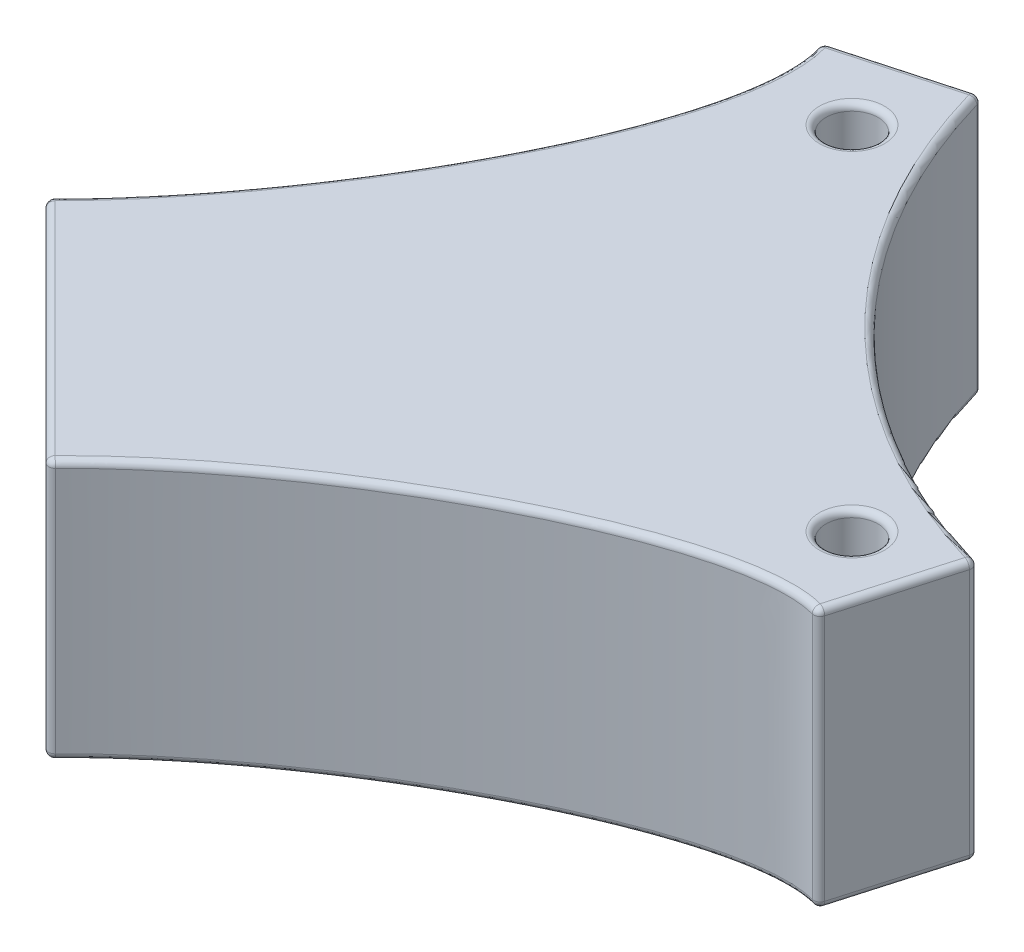
SolidWorks part; units mm, degrees
ref_plane "Front Plane" through (0, 0, 0) normal (0, 0, 1) x (1, 0, 0)
ref_plane "Top Plane" through (0, 0, 0) normal (0, 1, 0) x (1, 0, 0)
ref_plane "Right Plane" through (0, 0, 0) normal (1, 0, 0) x (0, 0, -1)
sketch "Sketch1" plane through (0, 0, 0) normal (0, 1, 0) x (1, 0, 0)
  line L0 (0, -254) -> (0, -279.4) construction
  line L5 (0, 0) -> (-269.2383, -74.6664) construction
  line L6 (0, 0) -> (-77.2319, -268.5137) construction
  line L7 (0, 0) -> (-279.4, 0) construction
  line L8 (0, 0) -> (-197.5656, -197.5656) construction
  line L9 (0, 0) -> (-106.9218, -258.1319) construction
  line L10 (0, 0) -> (-258.1319, -106.9218) construction
  line L11 (-220.2859, -61.0907) -> (-269.2383, -74.6664)
  line L12 (-63.1897, -219.693) -> (-77.2319, -268.5137)
  line L13 (0, 0) -> (-323.2892, -323.2892) construction
  line L14 (-368.1905, -278.3879) -> (-278.3879, -368.1905)
  arc A0 (-220.2859, -61.0907) -> (-63.1897, -219.693) centre (0, 0) ccw
  arc A1 (-269.2383, -74.6664) -> (-77.2319, -268.5137) centre (0, 0) ccw
  arc A2 (-244.7621, -67.8785) -> (-70.2108, -244.1033) centre (0, 0) ccw construction
  circle A3 centre (-234.6654, -97.2016) radius 10.16
  circle A4 centre (-97.2016, -234.6654) radius 10.16
  circle A5 centre (0, 0) radius 279.4 construction
  circle A6 centre (0, 0) radius 228.6 construction
  spline S0 degree 3 poles (-269.2383, -74.6664) (-254.0063, -115.9218) (-312.7788, -224.0275) (-368.1905, -278.3879) knots 0 0 0 0 1 1 1 1
  spline S1 degree 3 poles (-77.2319, -268.5137) (-114.5477, -254.9241) (-223.2886, -310.8524) (-278.3879, -368.1905) knots 0 0 0 0 1 1 1 1
  point P25 (-323.2892, -323.2892)
  dimension "D1" = 457.2
  dimension "D6" = 508
  dimension "D7" = 20.32
  dimension "D8" = 20.32
  dimension "D3" = 22.5
  dimension "D4" = 22.5
  dimension "D5" = 45
  dimension "D9" = 7
  dimension "D10" = 6.453
  dimension "D11" = 45
  dimension "D12" = 127
  dimension "D13" = 90
  dimension "D14" = 457.2
  dimension "D2" = 50.8
extrude "Boss-Extrude1" add sketch "Sketch1" along normal blind 101.6 contours S1 A1 S0 L14 | S1 L12 A0 L11 S0 A1 A4 A3 region at (-173.6917, 0, 171.9635) region at (-250.9873, 0, 250.7567)
sketch "Sketch3" plane through (-323.2892, 0, 323.2892) normal (-0.7071, 0, 0.7071) x (0.7071, 0, 0.7071)
  line L0 (-63.5, 101.6) -> (63.5, 101.6) construction
  line L1 (-50.8, 88.9) -> (-25.4, 88.9)
  line L2 (-50.8, 88.9) -> (-50.8, 63.5)
  line L3 (-50.8, 63.5) -> (-25.4, 63.5)
  line L4 (-25.4, 88.9) -> (-25.4, 63.5)
  line L5 (-50.8, 38.1) -> (-25.4, 38.1)
  line L6 (-50.8, 38.1) -> (-50.8, 12.7)
  line L7 (-50.8, 12.7) -> (-25.4, 12.7)
  line L8 (-25.4, 38.1) -> (-25.4, 12.7)
  line L9 (25.4, 88.9) -> (50.8, 88.9)
  line L10 (25.4, 88.9) -> (25.4, 63.5)
  line L11 (25.4, 63.5) -> (50.8, 63.5)
  line L12 (50.8, 88.9) -> (50.8, 63.5)
  line L13 (25.4, 38.1) -> (50.8, 38.1)
  line L14 (25.4, 38.1) -> (25.4, 12.7)
  line L15 (25.4, 12.7) -> (50.8, 12.7)
  line L16 (50.8, 38.1) -> (50.8, 12.7)
  line L17 (-63.5, 101.6) -> (-63.5, 0) construction
  line L18 (-63.5, 0) -> (63.5, 0) construction
  line L19 (63.5, 101.6) -> (63.5, 0) construction
  dimension "D1" = 25.4
  dimension "D2" = 25.4
  dimension "D3" = 12.7
  dimension "D4" = 12.7
  dimension "D5" = 25.4
  dimension "D6" = 25.4
  dimension "D7" = 12.7
  dimension "D8" = 12.7
  dimension "D9" = 12.7
  dimension "D10" = 12.7
  dimension "D11" = 25.4
  dimension "D12" = 25.4
  dimension "D13" = 25.4
  dimension "D14" = 25.4
  dimension "D15" = 12.7
  dimension "D16" = 12.7
extrude "Cut-Extrude1" cut sketch "Sketch3" against normal blind 63.5
fillet "Fillet1" radius 2.54 38 edges at (-269.2383, 50.8, 74.6664) (-220.2859, 50.8, 61.0907) (-63.1897, 50.8, 219.693) (-77.2319, 50.8, 268.5137) (-368.1905, 50.8, 278.3879) (-278.3879, 50.8, 368.1905) (-341.2497, 76.2, 305.3287) (-350.23, 88.9, 296.3485) (-359.2102, 76.2, 287.3682) (-350.23, 63.5, 296.3485) (-287.3682, 25.4, 359.2102) (-296.3485, 38.1, 350.23) (-305.3287, 25.4, 341.2497) (-296.3485, 12.7, 350.23) (-287.3682, 76.2, 359.2102) (-296.3485, 88.9, 350.23) (-305.3287, 76.2, 341.2497) (-296.3485, 63.5, 350.23) (-341.2497, 25.4, 305.3287) (-350.23, 38.1, 296.3485) (-359.2102, 25.4, 287.3682) (-350.23, 12.7, 296.3485) (-234.6654, 0, 107.3616) (-97.2016, 0, 244.8254) (-70.2108, 0, 244.1033) (-162.4139, 0, 160.8716) (-244.7621, 0, 67.8785) (-323.2892, 0, 323.2892) (-234.6654, 101.6, 107.3616) (-97.2016, 101.6, 244.8254) (-323.2892, 101.6, 323.2892) (-244.7621, 101.6, 67.8785) (-162.4139, 101.6, 160.8716) (-70.2108, 101.6, 244.1033)
